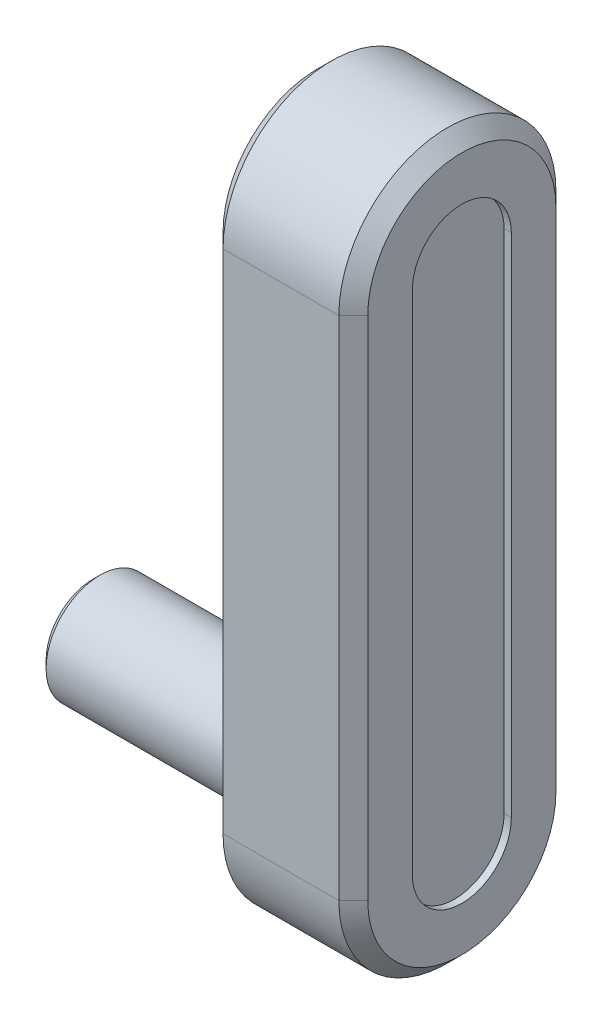
SolidWorks part; units mm, degrees
ref_plane "前视基准面" through (0, 0, 0) normal (0, 0, 1) x (1, 0, 0)
ref_plane "上视基准面" through (0, 0, 0) normal (0, 1, 0) x (1, 0, 0)
ref_plane "右视基准面" through (0, 0, 0) normal (1, 0, 0) x (0, 0, -1)
other "Configuration Table"
sketch "草图1" plane through (0, 0, 0) normal (1, 0, 0) x (0, 0, -1)
  circle A0 centre (0, 0) radius 4.9
  dimension "D1" = 9.8
extrude "凸台-拉伸1" add sketch "草图1" along normal blind 10
sketch "草图2" plane through (10, 0, 0) normal (1, 0, 0) x (0, 0, -1)
  line L0 (0, 0) -> (0, -70) construction
  line L1 (15, 0) -> (15, -70)
  line L2 (-15, 0) -> (-15, -70)
  arc A1 (15, 0) -> (-15, 0) centre (0, 0) ccw
  arc A2 (-15, -70) -> (15, -70) centre (0, -70) ccw
  point P3 (0, -35)
  dimension "D1" = 15
  dimension "D2" = 70
extrude "凸台-拉伸2" add sketch "草图2" along normal blind 20
sketch "草图3" plane through (10, 0, 0) normal (-1, 0, 0) x (0, 0, 1)
  circle A0 centre (0, -70) radius 7.45
  dimension "D1" = 14.9
extrude "凸台-拉伸3" add sketch "草图3" along normal blind 31
chamfer "倒角1" distance 2 angle 45 8 edges at (10, -35, -15) (10, 15, 0) (10, -85, 0) (10, -35, 15) (30, -35, -15) (30, 15, 0) (30, -85, 0) (30, -35, 15)
sketch "草图4" plane through (30, 0, 0) normal (1, 0, 0) x (0, 0, -1)
  line L0 (0, 0) -> (0, -70) construction
  line L1 (6.8356, 0) -> (6.8356, -70)
  line L2 (-6.8356, 0) -> (-6.8356, -70)
  arc A0 (6.8356, 0) -> (-6.8356, 0) centre (0, 0) ccw
  arc A1 (-6.8356, -70) -> (6.8356, -70) centre (0, -70) ccw
  point P4 (0, -35)
extrude "切除-拉伸1" cut sketch "草图4" against normal blind 1
sketch "草图5" plane through (0, 0, 0) normal (-1, 0, 0) x (0, 0, 1)
  circle A0 centre (0, 0) radius 4.9
extrude "切除-拉伸2" cut sketch "草图5" against normal blind 25
sketch "草图9" plane through (10, 0, 0) normal (-1, 0, 0) x (0, 0, 1)
  circle A0 centre (0, -70) radius 10
extrude "凸台-拉伸4" add sketch "草图9" along normal blind 1
chamfer "倒角2" distance 1 angle 45 1 edges at (9, -70, 10)
chamfer "倒角4" distance 1 angle 45 1 edges at (10, 0, -4.9)
chamfer "倒角5" distance 1 angle 45 1 edges at (-21, -70, 7.45)
